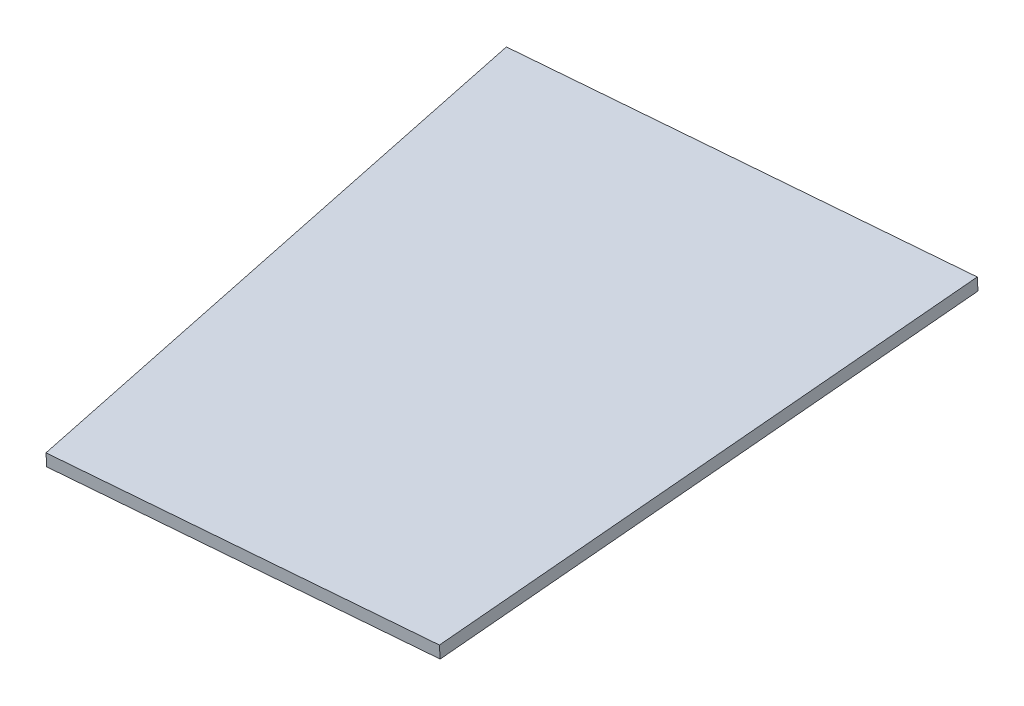
SolidWorks part; units mm, degrees
ref_plane "Front Plane" through (0, 0, 0) normal (0, 0, 1) x (1, 0, 0)
ref_plane "Top Plane" through (0, 0, 0) normal (0, 1, 0) x (1, 0, 0)
ref_plane "Right Plane" through (0, 0, 0) normal (1, 0, 0) x (0, 0, -1)
ref_plane "Pedlabox Floor Plane" through (2.2793, 231.1286, 15.8112) normal (-0.0098, -0.9976, -0.0682) x (-1, 0.0099, 0.0001)
sketch "PedalBox Floor" plane through (2.2793, 231.1286, 15.8112) normal (-0.0098, -0.9976, -0.0682) x (-1, 0.0099, 0.0001)
  line L0 (822.5611, -1122.2552) -> (810.1729, -1673.1441)
  line L1 (810.1729, -1673.1441) -> (1171.7257, -1704.8097)
  line L2 (1171.7257, -1704.8097) -> (1255.2877, -1160.1544)
  line L3 (1255.2877, -1160.1544) -> (822.5611, -1122.2552)
  line L4 (1225.8799, -1157.5788) -> (851.9689, -1124.8308) construction
  line L9 (1172.5328, -1699.5491) -> (1285.084, -965.9431) construction
  line L10 (826.9784, -925.8212) -> (810.2925, -1667.8233) construction
  line L11 (1171.8667, -1704.822) -> (810.0318, -1673.1317) construction
extrude "Boss-Extrude1" add sketch "PedalBox Floor" along normal blind 12.7 contours L3 L0 L1 L2
